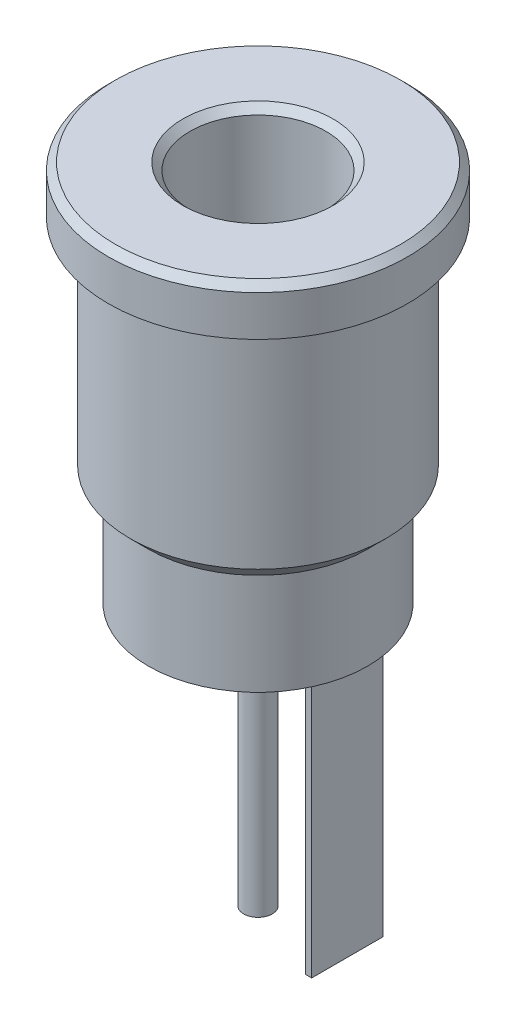
SolidWorks part; units mm, degrees
ref_plane "Front" through (0, 0, 0) normal (0, 0, 1) x (1, 0, 0)
ref_plane "Top" through (0, 0, 0) normal (0, 1, 0) x (1, 0, 0)
ref_plane "Right" through (0, 0, 0) normal (1, 0, 0) x (0, 0, -1)
sketch "Sketch1" plane through (0, 0, 0) normal (0, 1, 0) x (1, 0, 0)
  circle A0 centre (0, 0) radius 5.35
  dimension "D1" = 10.7
extrude "Boss-Extrude1" add sketch "Sketch1" along normal blind 14
sketch "Sketch2" plane through (0, 14, 0) normal (0, 1, 0) x (1, 0, 0)
  circle A0 centre (0, 0) radius 6.275
  dimension "D1" = 12.55
extrude "Boss-Extrude2" add sketch "Sketch2" along normal blind 2
sketch "Sketch3" plane through (0, 16, 0) normal (0, 1, 0) x (1, 0, 0)
  circle A0 centre (0, 0) radius 2.85
  dimension "D1" = 5.7
extrude "Cut-Extrude1" cut sketch "Sketch3" against normal blind 11.9
sketch "Sketch4" plane through (0, 4.1, 0) normal (0, 1, 0) x (1, 0, 0)
  circle A0 centre (0, 0) radius 1
  dimension "D1" = 2
extrude "Boss-Extrude3" add sketch "Sketch4" along normal offset from surface (8.9 mm away) 3 up to face at (0, 16, 2.85)
fillet "Fillet1" radius 1 1 edges at (0, 13, 1)
chamfer "Chamfer1" distance 0.3 angle 45 2 edges at (0, 16, 6.275) (0, 16, 2.85)
sketch "Sketch5" plane through (0, 0, 0) normal (0, -1, 0) x (1, 0, 0)
  circle A0 centre (0, 0) radius 5.35
  circle A1 centre (0, 0) radius 4.6
  circle A2 centre (0, 0) radius 5.35 construction
  dimension "D1" = 9.2
extrude "Cut-Extrude2" cut sketch "Sketch5" against normal blind 4
chamfer "Chamfer2" distance 1 angle 45 1 edges at (0, 4, -5.35)
sketch "Sketch6" plane through (0, 0, 0) normal (0, -1, 0) x (1, 0, 0)
  line L0 (0, 0) -> (8.6558, 0) construction
  line L2 (3.5, 1.5) -> (3.75, 1.5)
  line L3 (3.5, 1.5) -> (3.5, -1.5)
  line L4 (3.5, -1.5) -> (3.75, -1.5)
  line L5 (3.75, 1.5) -> (3.75, -1.5)
  line L6 (3.5, 1.5) -> (3.75, -1.5) construction
  line L7 (3.5, -1.5) -> (3.75, 1.5) construction
  circle A0 centre (0, 0) radius 0.6
  point P3 (3.625, 0)
  dimension "D4" = 1.2
  dimension "D1" = 0.25
  dimension "D2" = 3
  dimension "D3" = 3.5
extrude "Boss-Extrude4" add sketch "Sketch6" along normal blind 11
